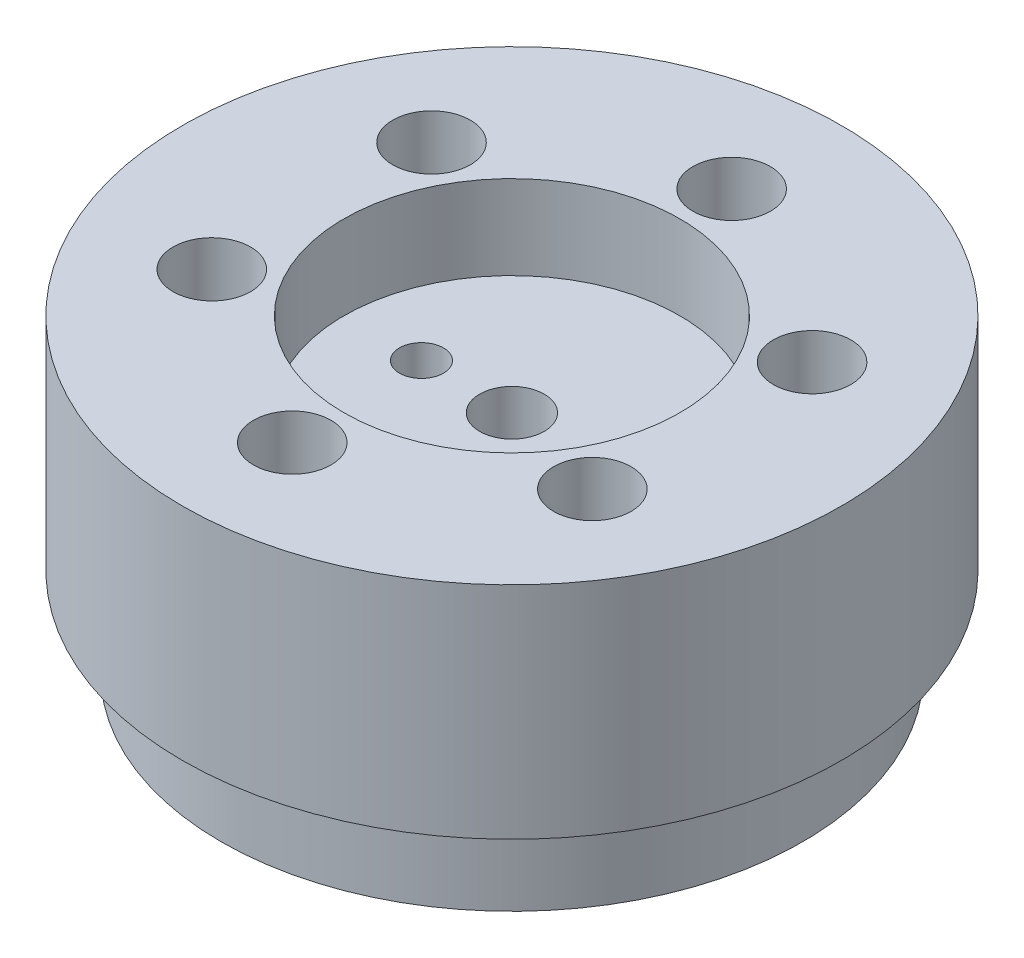
SolidWorks part; units mm, degrees
ref_plane "Front Plane" through (0, 0, 0) normal (0, 0, 1) x (1, 0, 0)
ref_plane "Top Plane" through (0, 0, 0) normal (0, 1, 0) x (1, 0, 0)
ref_plane "Right Plane" through (0, 0, 0) normal (1, 0, 0) x (0, 0, -1)
sketch "Sketch2" plane through (0, 0, 0) normal (0, 1, 0) x (1, 0, 0)
  line L1 (-11.3021, -6.4235) -> (11.3021, -6.4235)
  line L2 (-11.3021, -6.4235) -> (-11.3021, 6.4235)
  line L3 (-11.3021, 6.4235) -> (11.3021, 6.4235)
  line L4 (11.3021, -6.4235) -> (11.3021, 6.4235)
  circle A0 centre (0, 0) radius 22.5
  circle A1 centre (0, 0) radius 13
  circle A2 centre (0, 0) radius 2.5
  circle A3 centre (-7, 0) radius 1.7
  circle A4 centre (7, 0) radius 1.7
  circle A5 centre (0, 17) radius 3
  circle A6 centre (0, -17) radius 3
  circle A7 centre (0, -17) radius 1.7
  circle A8 centre (0, 17) radius 1.7
  circle A9 centre (-14.7224, -8.5) radius 1.7
  circle A10 centre (-14.7224, -8.5) radius 3
  circle A11 centre (-14.7224, 8.5) radius 1.7
  circle A12 centre (-14.7224, 8.5) radius 3
  circle A13 centre (0, 17) radius 1.7 [skipped]
  circle A14 centre (0, 17) radius 3 [skipped]
  circle A15 centre (14.7224, 8.5) radius 1.7
  circle A16 centre (14.7224, 8.5) radius 3
  circle A17 centre (14.7224, -8.5) radius 1.7
  circle A18 centre (14.7224, -8.5) radius 3
  circle A19 centre (0, 0) radius 17 construction
  point P37 (0, 0)
  dimension "D1" = 26
  dimension "D2" = 5
  dimension "D3" = 7
  dimension "D5" = 6
  dimension "D6" = 6
  dimension "D9" = 6
  dimension "D10" = 3.4
  dimension "D7" = 34
  dimension "D8" = 3.4
  dimension "D4" = 7
extrude "Boss-Extrude1" add sketch "Sketch2" along normal blind 20 contours A1 | A0 A1 | A4 | A3 | A5 | A6 | A1 region at (0, 0, -9.1211) region at (-21.8636, 0, 0) region at (-7, 0, 0) region at (7, 0, 0) region at (-2.9151, 0, -17) region at (-2.9151, 0, 17)
extrude "Boss-Extrude4" add sketch "Sketch2<6>" along normal blind 24 contours A0 A1 | A5 | A6 region at (-21.8636, 0, 0) region at (-2.9151, 0, -17) region at (-2.9151, 0, 17)
sketch "Sketch2<6>" plane through (0, 0, 0) normal (0, 1, 0) x (1, 0, 0) same geometry as "Sketch2"
extrude "Cut-Extrude1" cut sketch "Sketch2<8>" along normal up to surface (20 mm away) contours L1 L4 L3 L2 A2 | A2 region at (-11.0421, 0, 0) region at (0, 0, 0) up to face at (0, 20, 13)
sketch "Sketch2<8>" plane through (0, 0, 0) normal (0, 1, 0) x (1, 0, 0) same geometry as "Sketch2"
extrude "Boss-Extrude6" add sketch "Sketch2<9>" along normal blind 20 contours L1 L4 L3 L2 A2 region at (-11.0421, 0, 0)
sketch "Sketch2<9>" plane through (0, 0, 0) normal (0, 1, 0) x (1, 0, 0) same geometry as "Sketch2"
extrude "Cut-Extrude2" cut sketch "Sketch2<10>" along normal blind 15 contours L1 L4 L3 L2 A4 A3 A2 region at (-11.0421, 0, 0)
sketch "Sketch2<10>" plane through (0, 0, 0) normal (0, 1, 0) x (1, 0, 0) same geometry as "Sketch2"
fillet "Fillet3" radius 3 4 edges at (11.3021, 7.5, 6.4235) (-11.3021, 7.5, 6.4235) (-11.3021, 7.5, -6.4235) (11.3021, 7.5, -6.4235)
extrude "Cut-Extrude3" cut sketch "Sketch2<11>" along normal up to surface (24 mm away) contours A5 | A6 region at (-2.9151, 0, -17) region at (-2.9151, 0, 17) up to face at (14.7224, 24, 11.5)
sketch "Sketch2<11>" plane through (0, 0, 0) normal (0, 1, 0) x (1, 0, 0) same geometry as "Sketch2"
sketch "Sketch3" plane through (0, 20, 0) normal (0, 1, 0) x (1, 0, 0)
  circle A0 centre (0, 0) radius 13
extrude "Cut-Extrude4" cut sketch "Sketch3" against normal blind 2.5
extrude "Boss-Extrude7" add sketch "Sketch2<13>" along normal offset from surface (10 mm away) 14 contours A10 A9 | A12 A11 | A16 A15 | A18 A17 | A5 A8 | A6 A7 region at (-2.9151, 0, -17) region at (-2.9151, 0, 17) region at (-17.6376, 0, 8.5) region at (-17.6376, 0, -8.5) region at (11.8073, 0, -8.5) region at (11.8073, 0, 8.5) up to face at (0, 24, -14)
sketch "Sketch2<13>" plane through (0, 0, 0) normal (0, 1, 0) x (1, 0, 0) same geometry as "Sketch2"
sketch "Sketch4" plane through (0, 0, 0) normal (0, -1, 0) x (1, 0, 0)
  circle A0 centre (0, 0) radius 22.5
  circle A2 centre (0, 0) radius 25.5
  dimension "D1" = 3
extrude "Boss-Extrude8" add sketch "Sketch4" along normal offset from surface (14 mm away) 10 from surface up to face at (0, 0, 22.5) starting at face at (0, 24, -14)
sketch "Sketch5" plane through (0, 10, 0) normal (0, 1, 0) x (1, 0, 0)
  line L0 (-14.7224, 8.5) -> (14.7224, -8.5) construction
  line L1 (-14.7224, -8.5) -> (14.7224, 8.5) construction
  line L2 (0, 17) -> (0, -17) construction
  circle A0 centre (14.7224, 8.5) radius 2.5
  circle A1 centre (14.7224, -8.5) radius 2.5
  circle A2 centre (0, -17) radius 2.5
  circle A3 centre (-14.7224, -8.5) radius 2.5
  circle A4 centre (-14.7224, 8.5) radius 2.5
  circle A5 centre (0, 17) radius 2.5
  circle A6 centre (14.7224, 8.5) radius 3
  circle A7 centre (14.7224, 8.5) radius 1.7
  circle A8 centre (14.7224, -8.5) radius 1.7
  circle A9 centre (14.7224, -8.5) radius 3
  circle A10 centre (0, -17) radius 1.7
  circle A11 centre (0, -17) radius 3
  circle A12 centre (-14.7224, -8.5) radius 1.7
  circle A13 centre (-14.7224, -8.5) radius 3
  circle A14 centre (-14.7224, 8.5) radius 1.7
  circle A15 centre (-14.7224, 8.5) radius 3
  circle A16 centre (0, 17) radius 1.7
  circle A17 centre (0, 17) radius 3
  circle A18 centre (0, 0) radius 17 construction
  point P15 (0, 0)
  point P33 (0, 0)
  circle M4 centre (14.7224, 8.5) radius 1.7
  circle M5 centre (14.7224, 8.5) radius 3
  dimension "D1" = 6
  dimension "D3" = 34
  dimension "D2" = 6
extrude "Boss-Extrude9" add sketch "Sketch5" along normal blind 2 contours A15 A4 | A4 A14 | A5 A16 | A17 A5 | A0 M4 | A0 M5 | A1 A8 | A9 A1 | A2 A10 | A11 A2 | A3 A12 | A13 A3 region at (12.2931, 10, -8.5) region at (12.2931, 10, 8.5) region at (-2.4293, 10, 17) region at (-17.1517, 10, 8.5) region at (-17.1517, 10, -8.5) region at (-2.4293, 10, -17) region at (11.8073, 10, -8.5) region at (11.8073, 10, 8.5) region at (-2.9151, 10, 17) region at (-17.6376, 10, 8.5) region at (-17.6376, 10, -8.5) region at (-2.9151, 10, -17)
sketch "Sketch6" plane through (0, 15, 0) normal (0, -1, 0) x (1, 0, 0)
  line L0 (11.3021, 3.4235) -> (11.3021, -3.4235)
  line L1 (8.3021, -6.4235) -> (-8.3021, -6.4235)
  line L2 (-11.3021, -3.4235) -> (-11.3021, 3.4235)
  line L3 (8.3021, 6.4235) -> (-8.3021, 6.4235)
  arc A0 (8.3021, 6.4235) -> (11.3021, 3.4235) centre (8.3021, 3.4235) cw
  arc A1 (11.3021, -3.4235) -> (8.3021, -6.4235) centre (8.3021, -3.4235) cw
  arc A2 (-8.3021, 6.4235) -> (-11.3021, 3.4235) centre (-8.3021, 3.4235) ccw
  arc A3 (-11.3021, -3.4235) -> (-8.3021, -6.4235) centre (-8.3021, -3.4235) ccw
  circle A4 centre (7, 0) radius 1.7
  circle A5 centre (0, 0) radius 2.5
  circle A6 centre (-7, 0) radius 1.7
  dimension "D1" = 5
  dimension "D2" = 3.4
  dimension "D3" = 3.4
extrude "Boss-Extrude10" add sketch "Sketch6" along normal blind 10
sketch "Sketch7" plane through (0, 5, 0) normal (0, -1, 0) x (1, 0, 0)
  circle A0 centre (-7, 0) radius 2.5
  circle A1 centre (7, 0) radius 2.5
  circle A3 centre (7, 0) radius 1.7
  circle A4 centre (-7, 0) radius 1.7
  dimension "D1" = 5
  dimension "D2" = 5
  dimension "D3" = 3.4
  dimension "D4" = 3.4
extrude "Cut-Extrude5" cut sketch "Sketch7" against normal blind 4
extrude "Boss-Extrude11" add sketch "Sketch4<2>" along normal blind 3.05 from surface starting at face at (0, 10, 25.5)
sketch "Sketch4<2>" plane through (0, 0, 0) normal (0, -1, 0) x (1, 0, 0) same geometry as "Sketch4"
